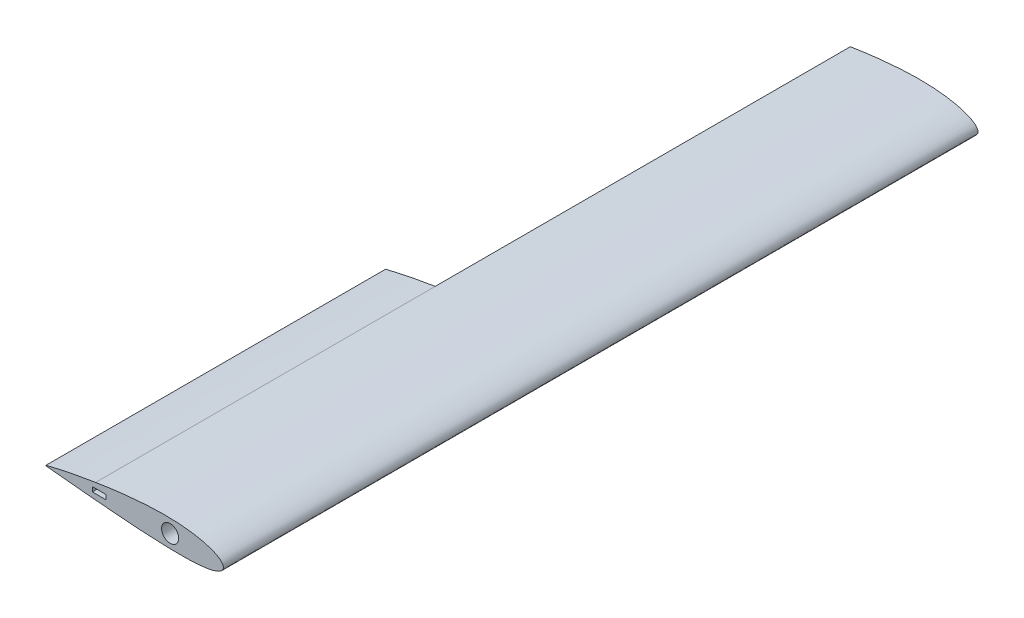
SolidWorks part; units mm, degrees
ref_plane "Front Plane" through (0, 0, 0) normal (0, 0, 1) x (1, 0, 0)
ref_plane "Top Plane" through (0, 0, 0) normal (0, 1, 0) x (1, 0, 0)
ref_plane "Right Plane" through (0, 0, 0) normal (1, 0, 0) x (0, 0, -1)
sketch "Sketch1" plane through (0, 0, 0) normal (0, 0, 1) x (1, 0, 0)
  line L0 (-189.5177, 15.2218) -> (-189.5177, -7.5941)
  spline S0 degree 3 poles (-189.5177, 15.2218) (-187.1369, 15.6014) (-181.5242, 16.4962) (-172.5795, 17.8022) (-162.6243, 19.1567) (-152.4681, 20.4133) (-142.1744, 21.5554) (-131.8072, 22.5613) (-121.4316, 23.4121) (-111.0981, 24.0888) (-100.8527, 24.5801) (-90.7586, 24.8093) (-80.8982, 24.774) (-71.3565, 24.4687) (-62.1976, 23.896) (-53.4829, 23.0627) (-45.2706, 21.981) (-37.6149, 20.6679) (-30.5654, 19.1446) (-24.1667, 17.4356) (-18.4578, 15.5683) (-13.4713, 13.5711) (-9.2335, 11.4718) (-5.7626, 9.2957) (-3.0694, 7.0598) (-1.1605, 4.7671) (-0.0625, 2.3959) (0.1432, -0.0144) (-0.535, -2.3343) (-2.0666, -4.442) (-4.3581, -6.3237) (-7.3821, -8.0146) (-11.1262, -9.5255) (-15.5729, -10.8568) (-20.6981, -12.0049) (-26.4717, -12.9669) (-32.8597, -13.7415) (-39.8243, -14.33) (-47.325, -14.7371) (-55.319, -14.9709) (-63.7608, -15.0426) (-72.6034, -14.9668) (-81.7972, -14.7606) (-91.2912, -14.4437) (-101.0512, -14.0339) (-111.0368, -13.559) (-121.1866, -12.9762) (-131.421, -12.31) (-141.6635, -11.5778) (-151.8521, -10.797) (-161.9248, -9.9836) (-171.82, -9.151) (-180.9981, -8.3559) (-186.8703, -7.8308) (-189.5177, -7.5941) knots 0 0 0 0 0.018424 0.043434 0.06908 0.095203 0.12164 0.148227 0.1748 0.201195 0.227364 0.253182 0.278347 0.30271 0.326128 0.348467 0.3696 0.389416 0.407811 0.424699 0.440008 0.453688 0.465715 0.476104 0.484928 0.49236 0.49873 0.504587 0.510443 0.516804 0.524199 0.532941 0.543186 0.554996 0.568376 0.583299 0.599709 0.617539 0.636704 0.657109 0.678651 0.701217 0.724685 0.748928 0.773811 0.799338 0.825326 0.851504 0.877716 0.9038 0.929596 0.954944 0.979688 1 1 1 1
extrude "Boss-Extrude1" add sketch "Sketch1" against normal blind 1120
sketch "Sketch2" plane through (0, 0, 0) normal (0, 0, 1) x (1, 0, 0)
  line L0 (-189.5177, 15.2218) -> (-189.5177, -7.5941)
  line L1 (-263.219, 0.4204) -> (-263.219, -0.4137)
  spline S0 degree 3 poles (-189.5177, 15.2218) (-190.2668, 15.1045) (-194.0251, 14.5158) (-200.6383, 13.3913) (-209.1995, 11.8813) (-217.2747, 10.3777) (-224.8169, 8.9107) (-231.7807, 7.4996) (-238.1249, 6.1663) (-243.8123, 4.9313) (-248.8094, 3.8144) (-253.0872, 2.8341) (-256.6212, 2.0071) (-259.3909, 1.3478) (-261.3806, 0.8681) (-262.5698, 0.579) (-263.0945, 0.4508) (-263.219, 0.4204) knots 0 0 0 0 0.030252 0.151774 0.267626 0.37709 0.479485 0.574175 0.66057 0.73813 0.806369 0.864859 0.913229 0.951173 0.978451 0.994887 1 1 1 1
  spline S1 degree 3 poles (-189.5177, -7.5941) (-189.9962, -7.5515) (-193.4821, -7.2417) (-199.8365, -6.6601) (-208.4252, -5.8654) (-216.5467, -5.0995) (-224.1497, -4.3713) (-231.1857, -3.6866) (-237.6098, -3.0518) (-243.3806, -2.4732) (-248.4606, -1.956) (-252.817, -1.5081) (-256.4209, -1.1292) (-259.2495, -0.8392) (-261.2822, -0.6051) (-262.5095, -0.5063) (-263.063, -0.4131) (-263.2098, -0.4136) (-263.219, -0.4137) knots 0 0 0 0 0.019463 0.141781 0.258505 0.3689 0.472262 0.567931 0.655294 0.733785 0.802892 0.862162 0.911205 0.949694 0.977373 0.994054 0.999628 1 1 1 1
extrude "Boss-Extrude2" add sketch "Sketch2" against normal blind 504
sketch "Sketch3" plane through (0, 0, 0) normal (0, 0, 1) x (1, 0, 0)
  circle A0 centre (-78.966, 4.935) radius 12.7
extrude "Cut-Extrude1" cut sketch "Sketch3" against normal blind 801
ref_plane "Plane1" through (0, 0, -376.7) normal (0, 0, 1) x (1, 0, 0)
sketch "Sketch4" plane through (0, 0, -376.7) normal (0, 0, 1) x (1, 0, 0)
  line L0 (-94.966, -15.812) -> (-62.966, -15.812)
  line L1 (-62.966, -15.812) -> (-62.966, 20.635)
  line L2 (-62.966, 20.635) -> (-94.966, 20.635)
  line L3 (-94.966, 20.635) -> (-94.966, -15.812)
extrude "Cut-Extrude2" cut sketch "Sketch4" along normal blind 46
ref_plane "Plane2" through (0, 0, -376.7) normal (0, 0, 1) x (1, 0, 0)
sketch "Sketch5" plane through (0, 0, -376.7) normal (0, 0, 1) x (1, 0, 0)
  line L0 (-240.5752, -7.706) -> (-180.5752, -7.706)
  line L1 (-180.5752, -7.706) -> (-180.5752, 4.294)
  line L2 (-180.5752, 4.294) -> (-240.5752, 4.294)
  line L3 (-240.5752, 4.294) -> (-240.5752, -7.706)
extrude "Cut-Extrude3" cut sketch "Sketch5" along normal blind 46
ref_plane "Plane3" through (0, 0, -598.5) normal (0, 0, 1) x (1, 0, 0)
sketch "Sketch6" plane through (0, 0, -598.5) normal (0, 0, 1) x (1, 0, 0)
  line L0 (-171.771, -14.359) -> (-117.771, -14.359)
  line L1 (-117.771, -14.359) -> (-117.771, 14.741)
  line L2 (-117.771, 14.741) -> (-171.771, 14.741)
  line L3 (-171.771, 14.741) -> (-171.771, -14.359)
extrude "Cut-Extrude4" cut sketch "Sketch6" along normal blind 64
ref_plane "Plane4" through (0, 0, -25.5) normal (0, 0, 1) x (1, 0, 0)
sketch "Sketch7" plane through (0, 0, -25.5) normal (0, 0, 1) x (1, 0, 0)
  line L0 (-194.454, 0.548) -> (-174.054, 0.548)
  line L1 (-174.054, 0.548) -> (-174.054, 7.348)
  line L2 (-174.054, 7.348) -> (-194.454, 7.348)
  line L3 (-194.454, 7.348) -> (-194.454, 0.548)
extrude "Cut-Extrude5" cut sketch "Sketch7" along normal blind 26
ref_plane "Plane5" through (0, 0, -930) normal (0, 0, 1) x (1, 0, 0)
sketch "Sketch8" plane through (0, 0, -930) normal (0, 0, 1) x (1, 0, 0)
  line L0 (-60, -15.979) -> (-40, -15.979)
  line L1 (-40, -15.979) -> (-40, -11.979)
  line L2 (-40, -11.979) -> (-60, -11.979)
  line L3 (-60, -11.979) -> (-60, -15.979)
extrude "Cut-Extrude6" cut sketch "Sketch8" along normal blind 20
